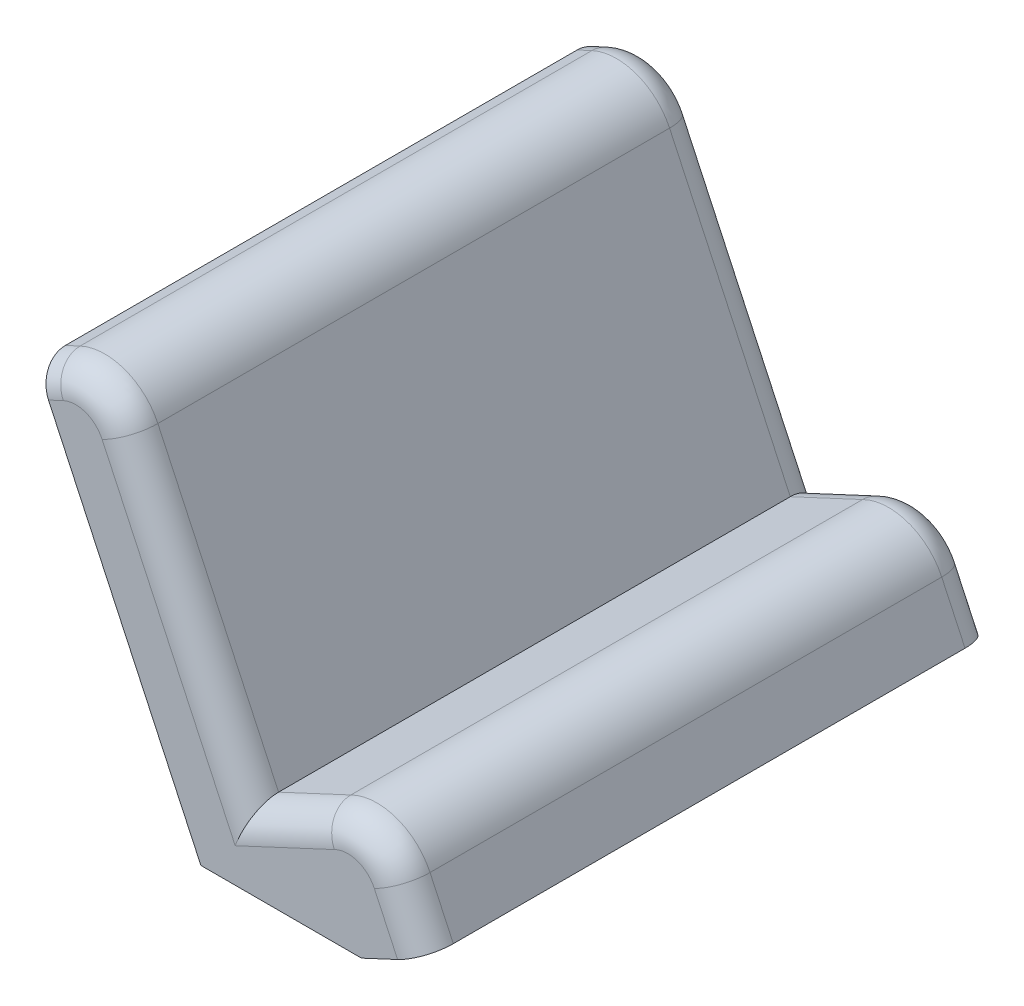
SolidWorks part; units mm, degrees
ref_plane "Front Plane" through (0, 0, 0) normal (0, 0, 1) x (1, 0, 0)
ref_plane "Top Plane" through (0, 0, 0) normal (0, 1, 0) x (1, 0, 0)
ref_plane "Right Plane" through (0, 0, 0) normal (1, 0, 0) x (0, 0, -1)
sketch "Sketch2" plane through (0, 0, 0) normal (0, 0, 1) x (1, 0, 0)
  line L7 (-55.9569, 120) -> (0, 0)
  line L8 (0, 0) -> (57.1, 0)
  line L9 (57.1, 0) -> (78.5451, 10)
  line L10 (78.5451, 10) -> (70.5741, 27.0939)
  line L11 (43.49, 36.5232) -> (18.7784, 25)
  line L12 (18.7784, 25) -> (-22.5046, 113.5315)
  line L14 (-55.9569, 120) -> (-49.0831, 123.2053)
  arc A1 (70.5741, 27.0939) -> (43.49, 36.5232) centre (52.4479, 18.6415) ccw
  arc A2 (-22.5046, 113.5315) -> (-49.0831, 123.2053) centre (-40.6307, 105.0792) ccw
  point P10 (-30.9569, 131.6577)
  dimension "D5" = 10
  dimension "D6" = 20
  dimension "D7" = 20
  dimension "D1" = 120
  dimension "D2" = 25
  dimension "D3" = 155
  dimension "D4" = 57.1
  dimension "D8" = 25
  dimension "D9" = 43.49
extrude "Boss-Extrude1" add sketch "Sketch2" along normal mid plane 195
sketch "Sketch3" plane through (0, 0, 0) normal (0, -1, 0) x (1, 0, 0)
  circle A0 centre (30, 0) radius 7.5
  dimension "D2" = 15
  dimension "D1" = 30
extrude "Boss-Extrude2" add sketch "Sketch3" along normal blind 10
fillet "Fillet1" radius 10 6 edges at (74.5596, 18.5469, 97.5) (-1.8631, 69.2658, 97.5) (-52.52, 121.6027, 97.5) (59.0238, 37.5295, 97.5) (31.1342, 30.7616, 97.5) (-33.7903, 123.873, 97.5)
fillet "Fillet2" radius 10 6 edges at (74.5596, 18.5469, -97.5) (-1.8631, 69.2658, -97.5) (-52.52, 121.6027, -97.5) (59.0238, 37.5295, -97.5) (31.1342, 30.7616, -97.5) (-33.7903, 123.873, -97.5)
chamfer "Chamfer1" distance 2 angle 45 5 edges at (-25.8654, 55.4685, -97.5) (-54.7191, 117.3455, -94.5711) (-55.9569, 120, 0) (-54.7191, 117.3455, 94.5711) (-25.8654, 55.4685, 97.5)
